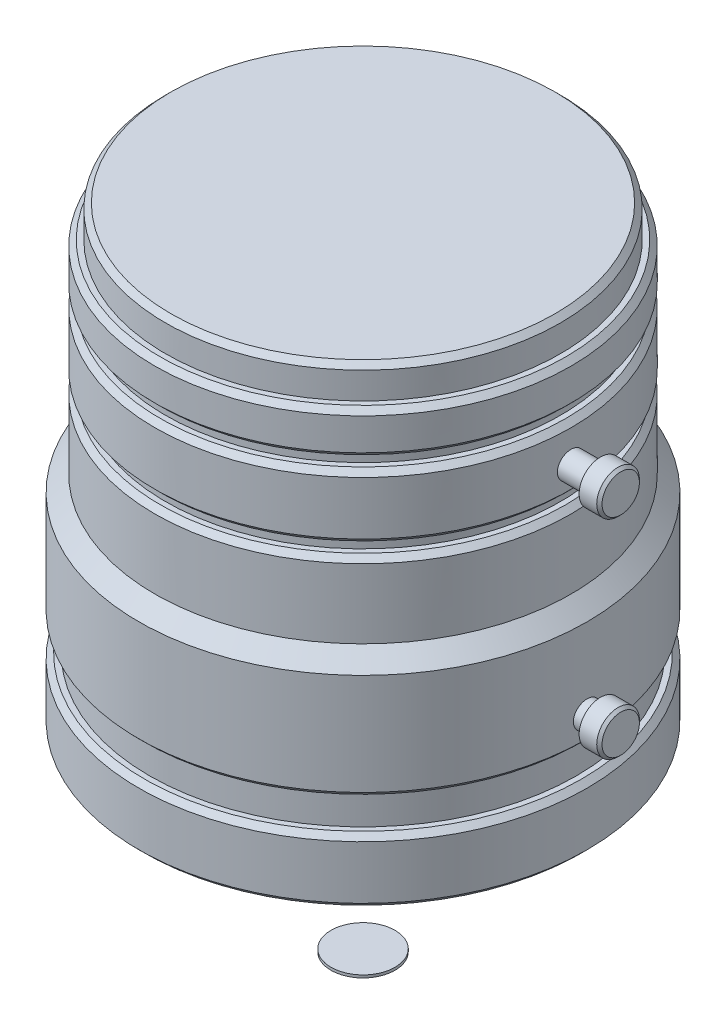
SolidWorks part; units mm, degrees
ref_plane "Front Plane" through (0, 0, 0) normal (0, 0, 1) x (1, 0, 0)
ref_plane "Top Plane" through (0, 0, 0) normal (0, 1, 0) x (1, 0, 0)
ref_plane "Right Plane" through (0, 0, 0) normal (1, 0, 0) x (0, 0, -1)
sketch "Sketch1" plane through (0, 0, 0) normal (0, 0, 1) x (1, 0, 0)
  line L0 (0, 0) -> (18.5, 0)
  line L1 (18.5, 0) -> (18.5, -3)
  line L2 (18.5, -3) -> (19.5, -3)
  line L3 (19.5, -3) -> (19.5, -7)
  line L4 (19.5, -7) -> (18.5, -7)
  line L5 (18.5, -7) -> (18.5, -8)
  line L6 (18.5, -8) -> (19.5, -8)
  line L7 (19.5, -8) -> (19.5, -14)
  line L8 (19.5, -14) -> (18.5, -14)
  line L9 (18.5, -14) -> (18.5, -15)
  line L10 (18.5, -15) -> (19.5, -15)
  line L11 (19.5, -15) -> (19.5, -22)
  line L12 (19.5, -22) -> (21, -22)
  line L13 (21, -22) -> (21, -33.5)
  line L14 (21, -33.5) -> (20, -33.5)
  line L15 (20, -33.5) -> (20, -36.5)
  line L16 (20, -36.5) -> (21, -36.5)
  line L17 (21, -36.5) -> (21, -42.5)
  line L18 (21, -42.5) -> (18, -42.5)
  line L19 (18, -42.5) -> (18, -43)
  line L20 (18, -43) -> (12.18, -43)
  line L21 (12.18, -43) -> (12.18, -43.75)
  line L22 (12.18, -43.75) -> (12.7, -43.75)
  line L23 (12.7, -43.75) -> (12.7, -47)
  line L24 (12.7, -47) -> (0, -47)
  line L25 (0, 0) -> (0, -47)
revolve "Lens Body" add sketch "Sketch1" angle 360 about L25
chamfer ".5mm Body Chamfers" distance 0.5 10 edges at (-18.5, 0, 0) (-19.5, -15, 0) (-19.5, -14, 0) (-19.5, -8, 0) (-19.5, -7, 0) (-19.5, -3, 0) (-21, -33.5, 0) (-21, -42.5, 0) (-21, -36.5, 0) (-18, -43, 0)
chamfer "1.5mm Body Chamfers" distance 1.5 angle 45 1 edges at (-21, -22, 0)
chamfer ".48mm x .28mm Body Chamfer 1" distance 0.28 distance2 0.48 1 edges at (-12.7, -43.75, 0) first distance on face at (-12.7, -43.75, 0)
chamfer ".48mm x .28mm Body Chamfer 2" distance 0.48 distance2 0.28 1 edges at (-12.7, -47, 0) first distance on face at (-12.7, -47, 0)
sketch "Sketch2" plane through (0, -47, 0) normal (0, -1, 0) x (1, 0, 0)
  circle A0 centre (0, 0) radius 9
extrude "Sensor Hole" cut sketch "Sketch2" against normal blind 10
sketch "Sketch7" plane through (0, 0, 0) normal (0, 0, 1) x (1, 0, 0)
  line L0 (20, -32.25) -> (22.25, -32.25)
  line L2 (22.25, -32.25) -> (22.25, -33)
  line L3 (22.25, -33) -> (24.15, -33)
  line L4 (24.15, -33) -> (24.15, -31)
  line L5 (20, -32.25) -> (20, -31)
  line L8 (24.15, -31) -> (20, -31)
revolve "Lower Knob" add sketch "Sketch7" angle 360 about L8
sketch "Sketch8" plane through (0, 0, 0) normal (0, 0, 1) x (1, 0, 0)
  line L1 (18.5, -12.75) -> (22.25, -12.75)
  line L2 (22.25, -12.75) -> (22.25, -13.5)
  line L3 (22.25, -13.5) -> (24.15, -13.5)
  line L4 (24.15, -13.5) -> (24.15, -11.5)
  line L5 (24.15, -11.5) -> (18.5, -11.5)
  line L6 (18.5, -11.5) -> (18.5, -12.75)
revolve "Upper Knob" add sketch "Sketch8" angle 360 about L5
chamfer ".25mm Upper Knob Chamfer" distance 0.25 1 edges at (24.15, -9.5, 0)
chamfer ".25mm Lower Knob Chamfer" distance 0.25 1 edges at (24.15, -31, -2)
ref_plane "Focal Plane" through (0, -60.78, 0) normal (0, 1, 0) x (1, 0, 0)
sketch "Sketch9" plane through (0, -60.78, 0) normal (0, 1, 0) x (1, 0, 0)
  circle A0 centre (0, 0) radius 3
extrude "Focal Point" add sketch "Sketch9" along normal blind 0.25 separate body
